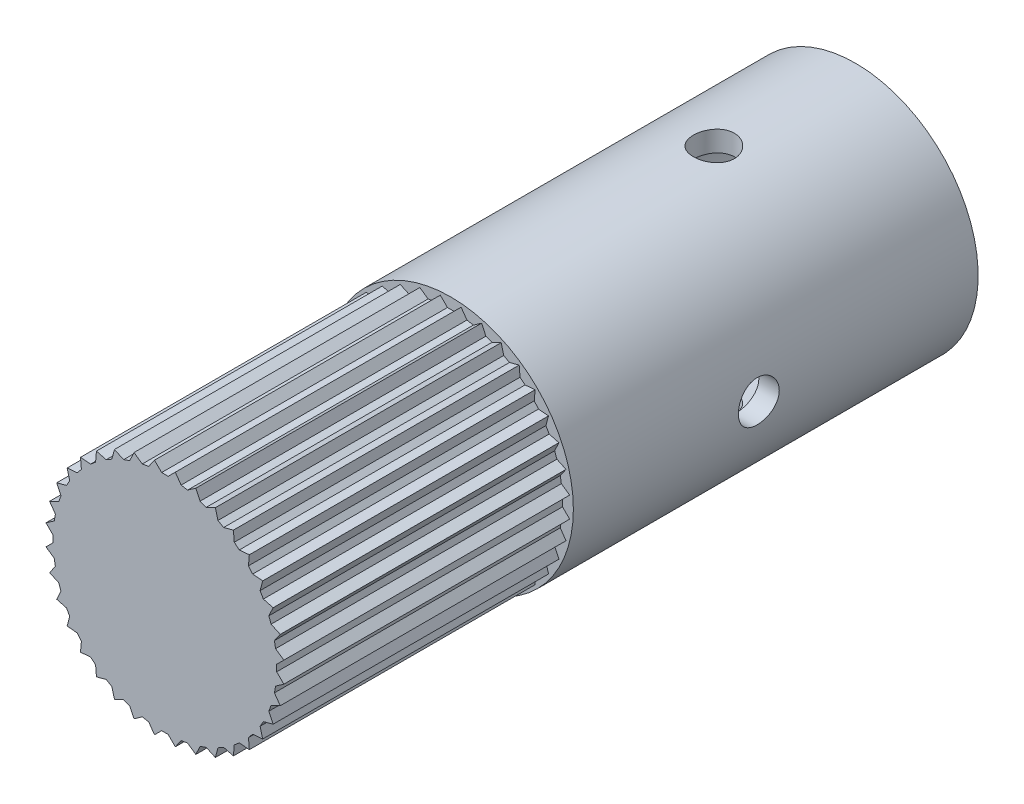
SolidWorks part; units mm, degrees
material "AISI 4130 Steel, annealed at 865C"
ref_plane "X-Y Datum" through (0, 0, 0) normal (0, 0, 1) x (1, 0, 0)
ref_plane "X-Z Datum" through (0, 0, 0) normal (0, 1, 0) x (1, 0, 0)
ref_plane "Y-Z Datum" through (0, 0, 0) normal (1, 0, 0) x (0, 0, -1)
sketch "Sketch9" plane through (0, 0, 0) normal (0, 1, 0) x (1, 0, 0)
  line L0 (16.002, 0) -> (0, 0)
  line L1 (0, 0) -> (0, -382.27)
  line L2 (0, -382.27) -> (-72.2493, -518.1512)
  dimension "D1" = 153.895
  dimension "D2" = 28
  dimension "D3" = 382.27
  dimension "D5" = 16.002
sketch "Sketch5" plane through (0, 0, 0) normal (0, 1, 0) x (1, 0, 0)
  line L0 (7.9375, -75.7961) -> (7.9375, -22.1615)
  line L1 (7.9375, -22.1615) -> (9.525, -22.1615)
  line L2 (9.525, -22.1615) -> (9.525, -75.7961)
  line L3 (9.525, -75.7961) -> (7.9375, -75.7961)
  line L5 (16.002, 0) -> (0, 0) construction
  line L6 (0, 0) -> (0, -382.27) construction
  line L7 (0, -382.27) -> (9.525, -382.27) construction
  line L8 (12.5602, -51.87) -> (0, -51.87) construction
  dimension "D1" = 1.5875
  dimension "D2" = 22.1615
  dimension "D3" = 7.9375
  dimension "D4" = 330.4
  dimension "D5" = 306.4739
revolve "Revolve2" add sketch "Sketch5" angle 360 about L1
sketch "Sketch6" plane through (0, 0, 0) normal (0, 1, 0) x (1, 0, 0)
  circle A0 centre (0, -33.1635) radius 1.5875 construction
  circle A1 centre (0, -33.1635) radius 1.5875
sketch "Sketch7" plane through (0, 0, 0) normal (1, 0, 0) x (0, 0, -1)
  circle A2 centre (-39.196, 0) radius 1.5875
  circle A4 centre (-39.196, 0) radius 1.5875 construction
extrude "Cut-Extrude5" cut sketch "Sketch7" against normal through all both and the other way through all
extrude "Cut-Extrude6" cut sketch "Sketch6" against normal through all both and the other way through all
sketch "Sketch8" plane through (0, 0, 0) normal (0, 0, 1) x (1, 0, 0)
  line L0 (9.2357, -0.808) -> (8.6817, -0.254)
  line L1 (8.6817, -0.254) -> (8.6817, 0.254)
  line L2 (8.6817, 0.254) -> (9.2357, 0.808)
  line L3 (8.6817, 0) -> (0, 0) construction
  line L4 (8.9551, -2.3995) -> (8.5057, -1.7577)
  line L5 (8.5057, -1.7577) -> (8.5939, -1.2574)
  line L6 (8.5939, -1.2574) -> (9.2357, -0.808)
  line L7 (8.4024, -3.9181) -> (8.0713, -3.208)
  line L8 (8.0713, -3.208) -> (8.245, -2.7306)
  line L9 (8.245, -2.7306) -> (8.9551, -2.3995)
  line L10 (7.5944, -5.3176) -> (7.3916, -4.5608)
  line L11 (7.3916, -4.5608) -> (7.6456, -4.1209)
  line L12 (7.6456, -4.1209) -> (8.4024, -3.9181)
  line L13 (6.5556, -6.5556) -> (6.4873, -5.7751)
  line L14 (6.4873, -5.7751) -> (6.8138, -5.3859)
  line L15 (6.8138, -5.3859) -> (7.5944, -5.3176)
  line L16 (5.3176, -7.5944) -> (5.3859, -6.8138)
  line L17 (5.3859, -6.8138) -> (5.7751, -6.4873)
  line L18 (5.7751, -6.4873) -> (6.5556, -6.5556)
  line L19 (3.9181, -8.4024) -> (4.1209, -7.6456)
  line L20 (4.1209, -7.6456) -> (4.5608, -7.3916)
  line L21 (4.5608, -7.3916) -> (5.3176, -7.5944)
  line L22 (2.3995, -8.9551) -> (2.7306, -8.245)
  line L23 (2.7306, -8.245) -> (3.208, -8.0713)
  line L24 (3.208, -8.0713) -> (3.9181, -8.4024)
  line L25 (0.808, -9.2357) -> (1.2574, -8.5939)
  line L26 (1.2574, -8.5939) -> (1.7577, -8.5057)
  line L27 (1.7577, -8.5057) -> (2.3995, -8.9551)
  line L28 (-0.808, -9.2357) -> (-0.254, -8.6817)
  line L29 (-0.254, -8.6817) -> (0.254, -8.6817)
  line L30 (0.254, -8.6817) -> (0.808, -9.2357)
  line L31 (-2.3995, -8.9551) -> (-1.7577, -8.5057)
  line L32 (-1.7577, -8.5057) -> (-1.2574, -8.5939)
  line L33 (-1.2574, -8.5939) -> (-0.808, -9.2357)
  line L34 (-3.9181, -8.4024) -> (-3.208, -8.0713)
  line L35 (-3.208, -8.0713) -> (-2.7306, -8.245)
  line L36 (-2.7306, -8.245) -> (-2.3995, -8.9551)
  line L37 (-5.3176, -7.5944) -> (-4.5608, -7.3916)
  line L38 (-4.5608, -7.3916) -> (-4.1209, -7.6456)
  line L39 (-4.1209, -7.6456) -> (-3.9181, -8.4024)
  line L40 (-6.5556, -6.5556) -> (-5.7751, -6.4873)
  line L41 (-5.7751, -6.4873) -> (-5.3859, -6.8138)
  line L42 (-5.3859, -6.8138) -> (-5.3176, -7.5944)
  line L43 (-7.5944, -5.3176) -> (-6.8138, -5.3859)
  line L44 (-6.8138, -5.3859) -> (-6.4873, -5.7751)
  line L45 (-6.4873, -5.7751) -> (-6.5556, -6.5556)
  line L46 (-8.4024, -3.9181) -> (-7.6456, -4.1209)
  line L47 (-7.6456, -4.1209) -> (-7.3916, -4.5608)
  line L48 (-7.3916, -4.5608) -> (-7.5944, -5.3176)
  line L49 (-8.9551, -2.3995) -> (-8.245, -2.7306)
  line L50 (-8.245, -2.7306) -> (-8.0713, -3.208)
  line L51 (-8.0713, -3.208) -> (-8.4024, -3.9181)
  line L52 (-9.2357, -0.808) -> (-8.5939, -1.2574)
  line L53 (-8.5939, -1.2574) -> (-8.5057, -1.7577)
  line L54 (-8.5057, -1.7577) -> (-8.9551, -2.3995)
  line L55 (-9.2357, 0.808) -> (-8.6817, 0.254)
  line L56 (-8.6817, 0.254) -> (-8.6817, -0.254)
  line L57 (-8.6817, -0.254) -> (-9.2357, -0.808)
  line L58 (-8.9551, 2.3995) -> (-8.5057, 1.7577)
  line L59 (-8.5057, 1.7577) -> (-8.5939, 1.2574)
  line L60 (-8.5939, 1.2574) -> (-9.2357, 0.808)
  line L61 (-8.4024, 3.9181) -> (-8.0713, 3.208)
  line L62 (-8.0713, 3.208) -> (-8.245, 2.7306)
  line L63 (-8.245, 2.7306) -> (-8.9551, 2.3995)
  line L64 (-7.5944, 5.3176) -> (-7.3916, 4.5608)
  line L65 (-7.3916, 4.5608) -> (-7.6456, 4.1209)
  line L66 (-7.6456, 4.1209) -> (-8.4024, 3.9181)
  line L67 (-6.5556, 6.5556) -> (-6.4873, 5.7751)
  line L68 (-6.4873, 5.7751) -> (-6.8138, 5.3859)
  line L69 (-6.8138, 5.3859) -> (-7.5944, 5.3176)
  line L70 (-5.3176, 7.5944) -> (-5.3859, 6.8138)
  line L71 (-5.3859, 6.8138) -> (-5.7751, 6.4873)
  line L72 (-5.7751, 6.4873) -> (-6.5556, 6.5556)
  line L73 (-3.9181, 8.4024) -> (-4.1209, 7.6456)
  line L74 (-4.1209, 7.6456) -> (-4.5608, 7.3916)
  line L75 (-4.5608, 7.3916) -> (-5.3176, 7.5944)
  line L76 (-2.3995, 8.9551) -> (-2.7306, 8.245)
  line L77 (-2.7306, 8.245) -> (-3.208, 8.0713)
  line L78 (-3.208, 8.0713) -> (-3.9181, 8.4024)
  line L79 (-0.808, 9.2357) -> (-1.2574, 8.5939)
  line L80 (-1.2574, 8.5939) -> (-1.7577, 8.5057)
  line L81 (-1.7577, 8.5057) -> (-2.3995, 8.9551)
  line L82 (0.808, 9.2357) -> (0.254, 8.6817)
  line L83 (0.254, 8.6817) -> (-0.254, 8.6817)
  line L84 (-0.254, 8.6817) -> (-0.808, 9.2357)
  line L85 (2.3995, 8.9551) -> (1.7577, 8.5057)
  line L86 (1.7577, 8.5057) -> (1.2574, 8.5939)
  line L87 (1.2574, 8.5939) -> (0.808, 9.2357)
  line L88 (3.9181, 8.4024) -> (3.208, 8.0713)
  line L89 (3.208, 8.0713) -> (2.7306, 8.245)
  line L90 (2.7306, 8.245) -> (2.3995, 8.9551)
  line L91 (5.3176, 7.5944) -> (4.5608, 7.3916)
  line L92 (4.5608, 7.3916) -> (4.1209, 7.6456)
  line L93 (4.1209, 7.6456) -> (3.9181, 8.4024)
  line L94 (6.5556, 6.5556) -> (5.7751, 6.4873)
  line L95 (5.7751, 6.4873) -> (5.3859, 6.8138)
  line L96 (5.3859, 6.8138) -> (5.3176, 7.5944)
  line L97 (7.5944, 5.3176) -> (6.8138, 5.3859)
  line L98 (6.8138, 5.3859) -> (6.4873, 5.7751)
  line L99 (6.4873, 5.7751) -> (6.5556, 6.5556)
  line L100 (8.4024, 3.9181) -> (7.6456, 4.1209)
  line L101 (7.6456, 4.1209) -> (7.3916, 4.5608)
  line L102 (7.3916, 4.5608) -> (7.5944, 5.3176)
  line L103 (8.9551, 2.3995) -> (8.245, 2.7306)
  line L104 (8.245, 2.7306) -> (8.0713, 3.208)
  line L105 (8.0713, 3.208) -> (8.4024, 3.9181)
  line L106 (9.2357, 0.808) -> (8.5939, 1.2574)
  line L107 (8.5939, 1.2574) -> (8.5057, 1.7577)
  line L108 (8.5057, 1.7577) -> (8.9551, 2.3995)
  circle A0 centre (0, 0) radius 12.7
  circle A1 centre (0, 0) radius 9.271 construction
  circle A2 centre (0, 0) radius 8.6854 construction
  point P153 (0, 0)
  dimension "D1" = 25.4
  dimension "D4" = 18.542
  dimension "D6" = 17.3708
  dimension "D2" = 0.508
  dimension "D3" = 135
  dimension "D5" = 36
ref_plane "Plane1" through (0, 0, 47.5615) normal (0, 0, -1) x (-1, 0, 0)
sketch "Sketch10" plane through (0, 0, 47.5615) normal (0, 0, -1) x (-1, 0, 0)
  circle A0 centre (0, 0) radius 7.9375
  dimension "D1" = 15.875
extrude "Boss-Extrude1" add sketch "Sketch10" against normal up to surface (28.2346 mm away) up to face at (-9.525, 0, 75.7961)
sketch "Sketch11" plane through (0, 0, 22.1615) normal (0, 0, -1) x (-1, 0, 0)
  line L0 (0, 9.525) -> (13.3548, 9.525) construction
  line L1 (0, 9.525) -> (0, 15.4312) construction
  line L2 (-9.525, 0) -> (-9.525, 9.1744) construction
  line L3 (-9.525, 0) -> (-16.674, 0) construction
  circle A0 centre (0, 0) radius 9.525 construction
  point P0 (0, 9.525)
  point P1 (-9.525, 0)
extrude "Cut-Extrude7" cut sketch "Sketch8" along normal blind 25.4 from offset 53.5991
